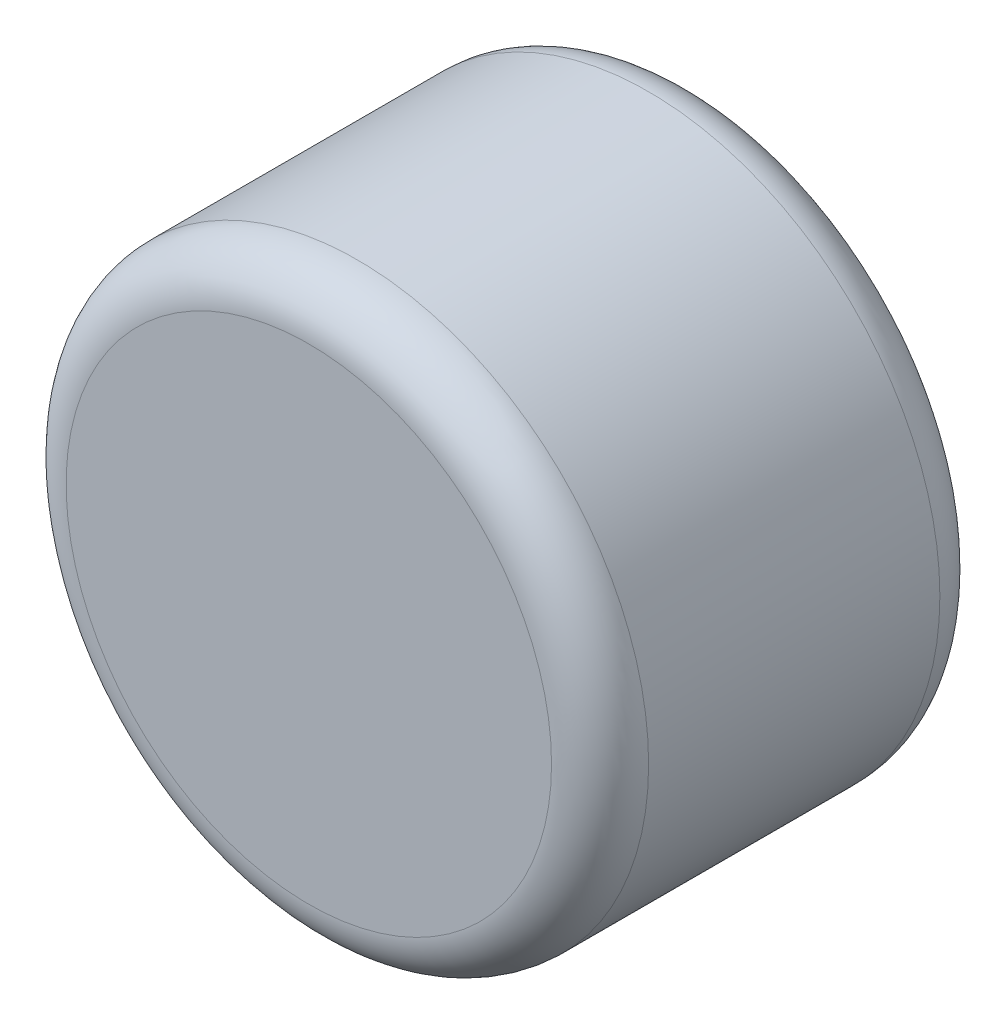
SolidWorks part; units mm, degrees
ref_plane "Piano frontale" through (0, 0, 0) normal (0, 0, 1) x (1, 0, 0)
ref_plane "Piano superiore" through (0, 0, 0) normal (0, 1, 0) x (1, 0, 0)
ref_plane "Piano destro" through (0, 0, 0) normal (1, 0, 0) x (0, 0, -1)
sketch "Schizzo1" plane through (0, 0, 0) normal (0, 0, 1) x (1, 0, 0)
  circle A0 centre (0, 0) radius 3
  dimension "D1" = 6
extrude "Estrusione-Estrusione1" add sketch "Schizzo1" along normal blind 4
fillet "Raccordo1" radius 0.5 2 edges at (3, 0, 0) (3, 0, 4)
equation "\"diametro_magnete\"= 6mm 'diametro magnete"
equation "\"altezza_magnete\"= 4 'altezza magnete"
equation "\"D1@Schizzo1\"= \"diametro_magnete\""
equation "\"D1@Estrusione-Estrusione1\"= \"altezza_magnete\""
